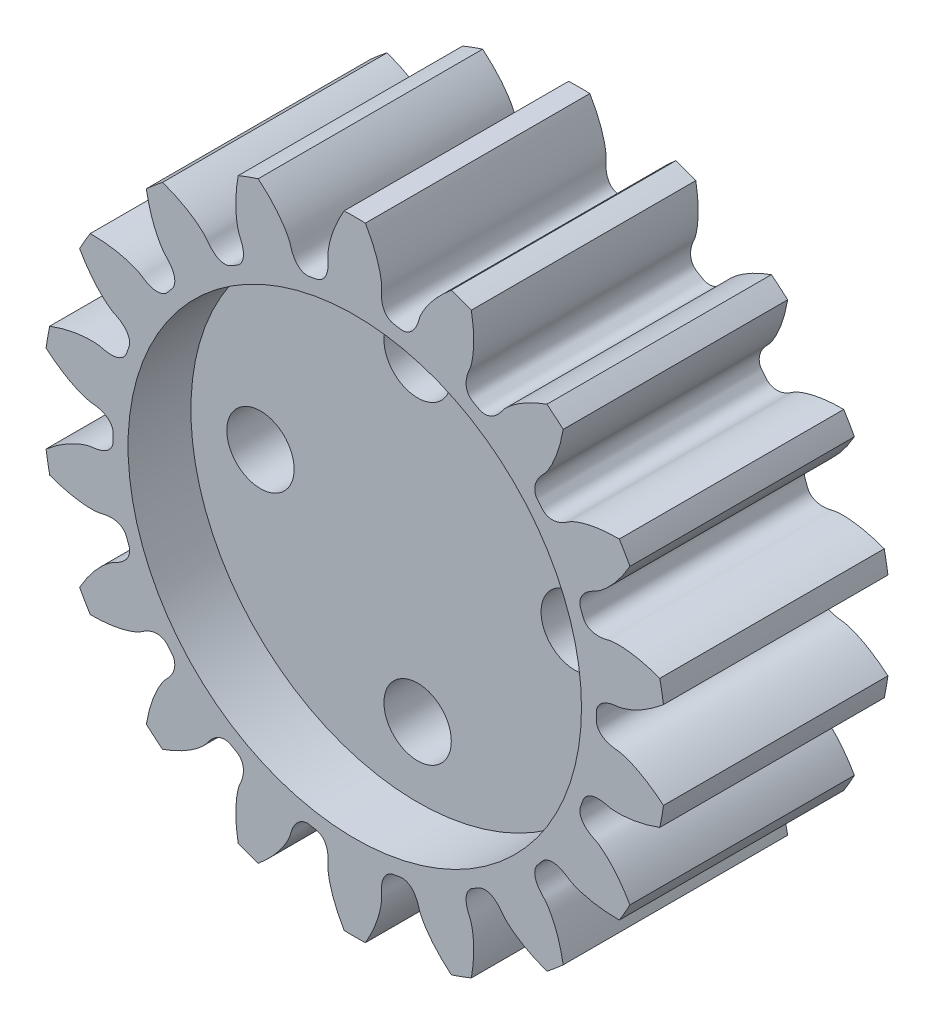
SolidWorks part; units mm, degrees
material "Д16 ГОСТ 4784-97"
ref_plane "FRONT" through (0, 0, 0) normal (0, 0, 1) x (1, 0, 0)
ref_plane "TOP" through (0, 0, 0) normal (0, 1, 0) x (1, 0, 0)
ref_plane "RIGHT" through (0, 0, 0) normal (1, 0, 0) x (0, 0, -1)
ref_axis "Ось1" through (0, 0, 50) along (0, 0, -1)
sketch "SketchRevolveSpurPinion" plane through (0, 0, 0) normal (1, 0, 0) x (0, 0, -1)
  line L0 (0, 0) -> (1, 0) construction
  line L1 (-9.525, 0) -> (-9.525, 13.8889)
  line L2 (-9.525, 13.8889) -> (0.475, 13.8889)
  line L3 (0.475, 13.8889) -> (0.475, 0)
  line L4 (0.475, 0) -> (-9.525, 0)
  dimension "D1" = 10
revolve "SpurPinion" add sketch "SketchRevolveSpurPinion" angle 360 about L0
sketch "SketchToothSpurPinion" plane through (0, 0, 0) normal (0, 0, 1) x (1, 0, 0)
  arc A0 (13.8146, 1.9979) -> (13.8146, -1.9979) centre (0, 0) cw
  spline S0 degree 3 poles (13.8146, -1.9979) (13.6988, -1.8974) (13.5252, -1.7559) (13.2912, -1.5837) (13.1267, -1.4705) (12.9688, -1.3692) (12.8181, -1.2792) (12.6752, -1.2) (12.5406, -1.1309) (12.4148, -1.0713) (12.2982, -1.0206) (12.1913, -0.9782) (12.0946, -0.9433) (12.0082, -0.9152) (11.9327, -0.8933) (11.8682, -0.8768) (11.815, -0.865) (11.7734, -0.8571) (11.7435, -0.8525) (11.7255, -0.8501) (11.69, -0.8469) (11.6475, -0.8436) (11.5944, -0.837) (11.5561, -0.8316) (11.5185, -0.8255) (11.4816, -0.8187) (11.4454, -0.8112) (11.4099, -0.803) (11.375, -0.794) (11.3408, -0.7844) (11.3072, -0.7739) (11.2742, -0.7626) (11.2418, -0.7505) (11.2099, -0.7375) (11.1786, -0.7236) (11.1477, -0.7087) (11.1174, -0.6927) (11.0876, -0.6755) (11.0582, -0.657) (11.0293, -0.637) (11.0009, -0.6155) (10.9731, -0.5923) (10.9459, -0.5672) (10.9194, -0.5399) (10.8939, -0.5103) (10.8695, -0.4783) (10.8465, -0.4436) (10.8254, -0.4061) (10.8065, -0.3659) (10.7903, -0.323) (10.7775, -0.2777) (10.7683, -0.2304) (10.7638, -0.1856) (10.7619, -0.1086) (10.7655, 0) (10.7619, 0.1086) (10.7638, 0.1856) (10.7683, 0.2304) (10.7775, 0.2777) (10.7903, 0.323) (10.8065, 0.3659) (10.8254, 0.4061) (10.8465, 0.4436) (10.8695, 0.4783) (10.8939, 0.5103) (10.9194, 0.5399) (10.9459, 0.5672) (10.9731, 0.5923) (11.0009, 0.6155) (11.0293, 0.637) (11.0582, 0.657) (11.0876, 0.6755) (11.1174, 0.6927) (11.1477, 0.7087) (11.1786, 0.7236) (11.2099, 0.7375) (11.2418, 0.7505) (11.2742, 0.7626) (11.3072, 0.7739) (11.3408, 0.7844) (11.375, 0.794) (11.4099, 0.803) (11.4454, 0.8112) (11.4816, 0.8187) (11.5185, 0.8255) (11.5561, 0.8316) (11.5944, 0.837) (11.6475, 0.8436) (11.69, 0.8469) (11.7255, 0.8501) (11.7435, 0.8525) (11.7734, 0.8571) (11.815, 0.865) (11.8682, 0.8768) (11.9327, 0.8933) (12.0082, 0.9152) (12.0946, 0.9433) (12.1913, 0.9782) (12.2982, 1.0206) (12.4148, 1.0713) (12.5406, 1.1309) (12.6752, 1.2) (12.8181, 1.2792) (12.9688, 1.3692) (13.1267, 1.4705) (13.2912, 1.5837) (13.5252, 1.7559) (13.6988, 1.8974) (13.8146, 1.9979) knots 0 0 0 0 0.059354 0.086688 0.11246 0.136671 0.159319 0.180405 0.19993 0.217892 0.234292 0.249131 0.262408 0.274122 0.284275 0.292866 0.299894 0.305361 0.309266 0.311609 0.31239 0.323048 0.32812 0.333111 0.338025 0.342864 0.347633 0.352337 0.35698 0.361569 0.366108 0.370606 0.375069 0.379506 0.383927 0.388343 0.392764 0.397204 0.401677 0.406198 0.410786 0.415456 0.420229 0.425124 0.430158 0.435351 0.440716 0.446263 0.451995 0.457908 0.463986 0.470203 0.476523 0.481419 0.5 0.518581 0.523477 0.529797 0.536014 0.542092 0.548005 0.553737 0.559284 0.564649 0.569842 0.574876 0.579771 0.584544 0.589214 0.593802 0.598323 0.602796 0.607236 0.611657 0.616073 0.620494 0.624931 0.629394 0.633892 0.638431 0.64302 0.647663 0.652367 0.657136 0.661975 0.666889 0.67188 0.676952 0.68761 0.688391 0.690734 0.694639 0.700106 0.707134 0.715725 0.725878 0.737592 0.750869 0.765708 0.782108 0.80007 0.819595 0.840681 0.863329 0.88754 0.913312 0.940646 1 1 1 1
extrude "ToothExtrudeCutSpurPinion" cut sketch "SketchToothSpurPinion" against normal blind 9.525 and the other way blind 9.525
pattern_circular "PatternSpurPinion" count 18 every 20 about axis through (0, 0, 50) along (0, 0, -1) of "ToothExtrudeCutSpurPinion"
sketch "AuxiliarySketchSpurPinion" plane through (0, 0, 0) normal (0, 0, 1) x (1, 0, 0)
  circle A0 centre (0, 0) radius 12.5 construction
  circle A1 centre (0, 0) radius 11.7462 construction
  circle A2 centre (0, 0) radius 11.7462 construction
  circle A3 centre (0, 0) radius 13.8889 construction
  circle A4 centre (0, 0) radius 10.7639 construction
  dimension "PitchDiameter" = 25
  dimension "BaseDiameter" = 23.4923
  dimension "FormDiameter" = 23.4923
  dimension "MajorDiameter" = 27.7778
  dimension "MinorDiameter" = 21.5278
sketch "Эскиз5" plane through (0, 0, 9.525) normal (0, 0, 1) x (1, 0, 0)
  circle A0 centre (0, 0) radius 10.1
extrude "Вырез-Вытянуть2" cut sketch "Эскиз5" against normal blind 2.8
sketch "Эскиз6" plane through (0, 0, 6.725) normal (0, 0, 1) x (1, 0, 0)
  circle A0 centre (0, 0) radius 7 construction
  circle A1 centre (0, 0) radius 8.5 construction
  circle A2 centre (0, 7) radius 1.5
  circle A3 centre (7, 0) radius 1.5
  circle A4 centre (0, -7) radius 1.5
  circle A5 centre (-7, 0) radius 1.5
  dimension "D1" = 14
  dimension "D2" = 17
extrude "Вырез-Вытянуть3" cut sketch "Эскиз6" against normal through all
